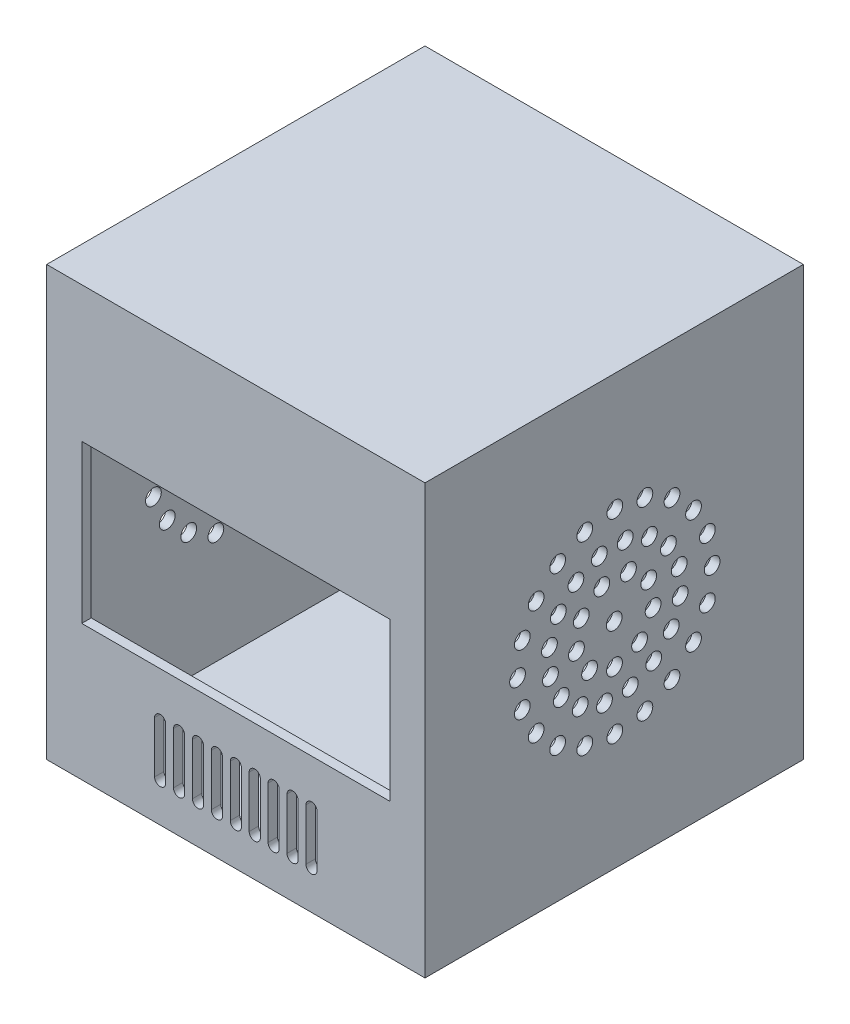
SolidWorks part; units mm, degrees
ref_plane "Front Plane" through (0, 0, 0) normal (0, 0, 1) x (1, 0, 0)
ref_plane "Top Plane" through (0, 0, 0) normal (0, 1, 0) x (1, 0, 0)
ref_plane "Right Plane" through (0, 0, 0) normal (1, 0, 0) x (0, 0, -1)
sketch "Sketch1" plane through (0, 0, 0) normal (0, 1, 0) x (1, 0, 0)
  line L1 (-60, 60) -> (60, 60)
  line L2 (-60, 60) -> (-60, -60)
  line L3 (-60, -60) -> (60, -60)
  line L4 (60, 60) -> (60, -60)
  line L5 (-60, 60) -> (60, -60) construction
  line L6 (-60, -60) -> (60, 60) construction
  line L11 (-55.2336, 55.2336) -> (55.2336, -55.2336) construction
  line L12 (-55.2336, -55.2336) -> (55.2336, 55.2336) construction
  line L13 (-57, 57) -> (57, 57)
  line L14 (-57, 57) -> (-57, -57)
  line L15 (-57, -57) -> (57, -57)
  line L16 (57, 57) -> (57, -57)
  line L17 (-57, 57) -> (57, -57) construction
  line L18 (-57, -57) -> (57, 57) construction
  point P0 (0, 0)
  point P6 (0, 0)
  point P11 (0, 0)
  dimension "D1" = 120
  dimension "D2" = 120
  dimension "D3" = 114
extrude "Boss-Extrude1" add sketch "Sketch1" along normal blind 130
sketch "Sketch2" plane through (0, 0, 60) normal (0, 0, 1) x (1, 0, 0)
  line L1 (-48.8667, 89.9707) -> (48.8667, 89.9707)
  line L2 (-48.8667, 89.9707) -> (-48.8667, 39.9707)
  line L3 (-48.8667, 39.9707) -> (48.8667, 39.9707)
  line L4 (48.8667, 89.9707) -> (48.8667, 39.9707)
  line L5 (-48.8667, 89.9707) -> (48.8667, 39.9707) construction
  line L6 (-48.8667, 39.9707) -> (48.8667, 89.9707) construction
  point P0 (0, 64.9707)
  dimension "D1" = 50
  dimension "D2" = 97.7334
extrude "Cut-Extrude2" cut sketch "Sketch2" against normal blind 19
sketch "Sketch3" plane through (0, 0, 0) normal (0, -1, 0) x (1, 0, 0)
  line L1 (-60, 60) -> (60, 60)
  line L2 (-60, 60) -> (-60, -60)
  line L3 (-60, -60) -> (60, -60)
  line L4 (60, 60) -> (60, -60)
  line L5 (-60, 60) -> (60, -60) construction
  line L6 (-60, -60) -> (60, 60) construction
  point P0 (0, 0)
extrude "Boss-Extrude3" add sketch "Sketch3" along normal blind 3
sketch "Sketch4" plane through (0, 130, 0) normal (0, 1, 0) x (1, 0, 0)
  line L1 (-60, 60) -> (60, 60)
  line L2 (-60, 60) -> (-60, -60)
  line L3 (-60, -60) -> (60, -60)
  line L4 (60, 60) -> (60, -60)
  line L5 (-60, 60) -> (60, -60) construction
  line L6 (-60, -60) -> (60, 60) construction
  point P0 (0, 0)
extrude "Boss-Extrude4" add sketch "Sketch4" along normal blind 3
sketch "Sketch6" plane through (60, 0, 0) normal (1, 0, 0) x (0, 0, -1)
  line L0 (-60, 133) -> (60, -3) construction
  line L1 (0.2085, 95.6425) -> (9.7439, 94.1322) construction
  line L2 (9.7439, 94.1322) -> (0.2085, 64.7855) construction
  line L3 (4.9762, 94.8874) -> (0.2085, 64.7855) construction
  line L4 (11.181, 82.6909) -> (0.2085, 64.7855) construction
  circle A0 centre (0, 65) radius 2.5
  circle A1 centre (0.2085, 64.7855) radius 35 construction
  circle A2 centre (0.2085, 95.6425) radius 2.5
  circle A3 centre (9.7439, 94.1322) radius 2.5
  circle A4 centre (18.3458, 89.7493) radius 2.5
  circle A5 centre (25.1724, 82.9228) radius 2.5
  circle A6 centre (29.5553, 74.3208) radius 2.5
  circle A7 centre (31.0656, 64.7855) radius 2.5
  circle A8 centre (29.5553, 55.2501) radius 2.5
  circle A9 centre (25.1724, 46.6482) radius 2.5
  circle A10 centre (18.3458, 39.8216) radius 2.5
  circle A11 centre (9.7439, 35.4387) radius 2.5
  circle A12 centre (0.2085, 33.9284) radius 2.5
  circle A13 centre (-9.3268, 35.4387) radius 2.5
  circle A14 centre (-17.9288, 39.8216) radius 2.5
  circle A15 centre (-24.7553, 46.6482) radius 2.5
  circle A16 centre (-29.1382, 55.2501) radius 2.5
  circle A17 centre (-30.6485, 64.7855) radius 2.5
  circle A18 centre (-29.1382, 74.3208) radius 2.5
  circle A19 centre (-24.7553, 82.9228) radius 2.5
  circle A20 centre (-17.9288, 89.7493) radius 2.5
  circle A21 centre (-9.3268, 94.1322) radius 2.5
  circle A22 centre (0.2085, 64.7855) radius 21 construction
  circle A23 centre (3.4937, 85.5269) radius 2.5
  circle A24 centre (11.181, 82.6909) radius 2.5
  circle A25 centre (17.1979, 77.1289) radius 2.5
  circle A26 centre (20.6283, 69.6878) radius 2.5
  circle A27 centre (20.95, 61.5003) radius 2.5
  circle A28 centre (18.114, 53.813) radius 2.5
  circle A29 centre (12.552, 47.7961) radius 2.5
  circle A30 centre (5.1109, 44.3657) radius 2.5
  circle A31 centre (-3.0766, 44.044) radius 2.5
  circle A32 centre (-10.7639, 46.88) radius 2.5
  circle A33 centre (-16.7808, 52.442) radius 2.5
  circle A34 centre (-20.2112, 59.8831) radius 2.5
  circle A35 centre (-20.5329, 68.0706) radius 2.5
  circle A36 centre (-17.6969, 75.7579) radius 2.5
  circle A37 centre (-12.135, 81.7748) radius 2.5
  circle A38 centre (-4.6938, 85.2052) radius 2.5
  circle A39 centre (0.2085, 64.7855) radius 12.3435 construction
  circle A40 centre (4.5285, 76.3483) radius 2.5
  circle A41 centre (10.9503, 70.8663) radius 2.5
  circle A42 centre (12.3459, 62.539) radius 2.5
  circle A43 centre (8.0622, 55.2628) radius 2.5
  circle A44 centre (0.1038, 52.4424) radius 2.5
  circle A45 centre (-7.8057, 55.3975) radius 2.5
  circle A46 centre (-11.9652, 62.7453) radius 2.5
  circle A47 centre (-10.4285, 71.0477) radius 2.5
  circle A48 centre (-3.9146, 76.42) radius 2.5
  point P4 (0, 0)
  point P52 (0.2085, 64.7855)
  point P92 (0.2085, 64.7855)
  point P104 (0.2085, 64.7855)
extrude "Cut-Extrude3" cut sketch "Sketch6" against normal through all
sketch "Sketch7" plane through (0, 0, 60) normal (0, 0, 1) x (1, 0, 0)
  line L0 (0, 25.6482) -> (0, 9.3516) construction
  line L1 (1.7671, 25.6482) -> (1.7671, 9.3516)
  line L2 (-1.7671, 25.6482) -> (-1.7671, 9.3516)
  line L3 (-53.7984, 17.4999) -> (55.7618, 17.4999) construction
  line L4 (6, 25.6482) -> (6, 9.3516) construction
  line L5 (7.7671, 25.6482) -> (7.7671, 9.3516)
  line L6 (4.2329, 25.6482) -> (4.2329, 9.3516)
  line L7 (12, 25.6482) -> (12, 9.3516) construction
  line L8 (13.7671, 25.6482) -> (13.7671, 9.3516)
  line L9 (10.2329, 25.6482) -> (10.2329, 9.3516)
  line L10 (18, 25.6482) -> (18, 9.3516) construction
  line L11 (19.7671, 25.6482) -> (19.7671, 9.3516)
  line L12 (16.2329, 25.6482) -> (16.2329, 9.3516)
  line L13 (24, 25.6482) -> (24, 9.3516) construction
  line L14 (25.7671, 25.6482) -> (25.7671, 9.3516)
  line L15 (22.2329, 25.6482) -> (22.2329, 9.3516)
  line L16 (-6, 25.6482) -> (-6, 9.3516) construction
  line L17 (-4.2329, 25.6482) -> (-4.2329, 9.3516)
  line L18 (-7.7671, 25.6482) -> (-7.7671, 9.3516)
  line L19 (-12, 25.6482) -> (-12, 9.3516) construction
  line L20 (-10.2329, 25.6482) -> (-10.2329, 9.3516)
  line L21 (-13.7671, 25.6482) -> (-13.7671, 9.3516)
  line L22 (-18, 25.6482) -> (-18, 9.3516) construction
  line L23 (-16.2329, 25.6482) -> (-16.2329, 9.3516)
  line L24 (-19.7671, 25.6482) -> (-19.7671, 9.3516)
  line L25 (-24, 25.6482) -> (-24, 9.3516) construction
  line L26 (-22.2329, 25.6482) -> (-22.2329, 9.3516)
  line L27 (-25.7671, 25.6482) -> (-25.7671, 9.3516)
  arc A0 (1.7671, 25.6482) -> (-1.7671, 25.6482) centre (0, 25.6482) ccw
  arc A1 (-1.7671, 9.3516) -> (1.7671, 9.3516) centre (0, 9.3516) ccw
  arc A2 (7.7671, 25.6482) -> (4.2329, 25.6482) centre (6, 25.6482) ccw
  arc A3 (4.2329, 9.3516) -> (7.7671, 9.3516) centre (6, 9.3516) ccw
  arc A4 (13.7671, 25.6482) -> (10.2329, 25.6482) centre (12, 25.6482) ccw
  arc A5 (10.2329, 9.3516) -> (13.7671, 9.3516) centre (12, 9.3516) ccw
  arc A6 (19.7671, 25.6482) -> (16.2329, 25.6482) centre (18, 25.6482) ccw
  arc A7 (16.2329, 9.3516) -> (19.7671, 9.3516) centre (18, 9.3516) ccw
  arc A8 (25.7671, 25.6482) -> (22.2329, 25.6482) centre (24, 25.6482) ccw
  arc A9 (22.2329, 9.3516) -> (25.7671, 9.3516) centre (24, 9.3516) ccw
  arc A10 (-4.2329, 25.6482) -> (-7.7671, 25.6482) centre (-6, 25.6482) ccw
  arc A11 (-7.7671, 9.3516) -> (-4.2329, 9.3516) centre (-6, 9.3516) ccw
  arc A12 (-10.2329, 25.6482) -> (-13.7671, 25.6482) centre (-12, 25.6482) ccw
  arc A13 (-13.7671, 9.3516) -> (-10.2329, 9.3516) centre (-12, 9.3516) ccw
  arc A14 (-16.2329, 25.6482) -> (-19.7671, 25.6482) centre (-18, 25.6482) ccw
  arc A15 (-19.7671, 9.3516) -> (-16.2329, 9.3516) centre (-18, 9.3516) ccw
  arc A16 (-22.2329, 25.6482) -> (-25.7671, 25.6482) centre (-24, 25.6482) ccw
  arc A17 (-25.7671, 9.3516) -> (-22.2329, 9.3516) centre (-24, 9.3516) ccw
  point P3 (0, 17.4999)
  point P14 (6, 17.4999)
  point P21 (12, 17.4999)
  point P28 (18, 17.4999)
  point P35 (24, 17.4999)
  point P42 (-6, 17.4999)
  point P49 (-12, 17.4999)
  point P56 (-18, 17.4999)
  point P63 (-24, 17.4999)
  dimension "D1" = 5
  dimension "D2" = 5
extrude "Cut-Extrude4" cut sketch "Sketch7" against normal blind 32
